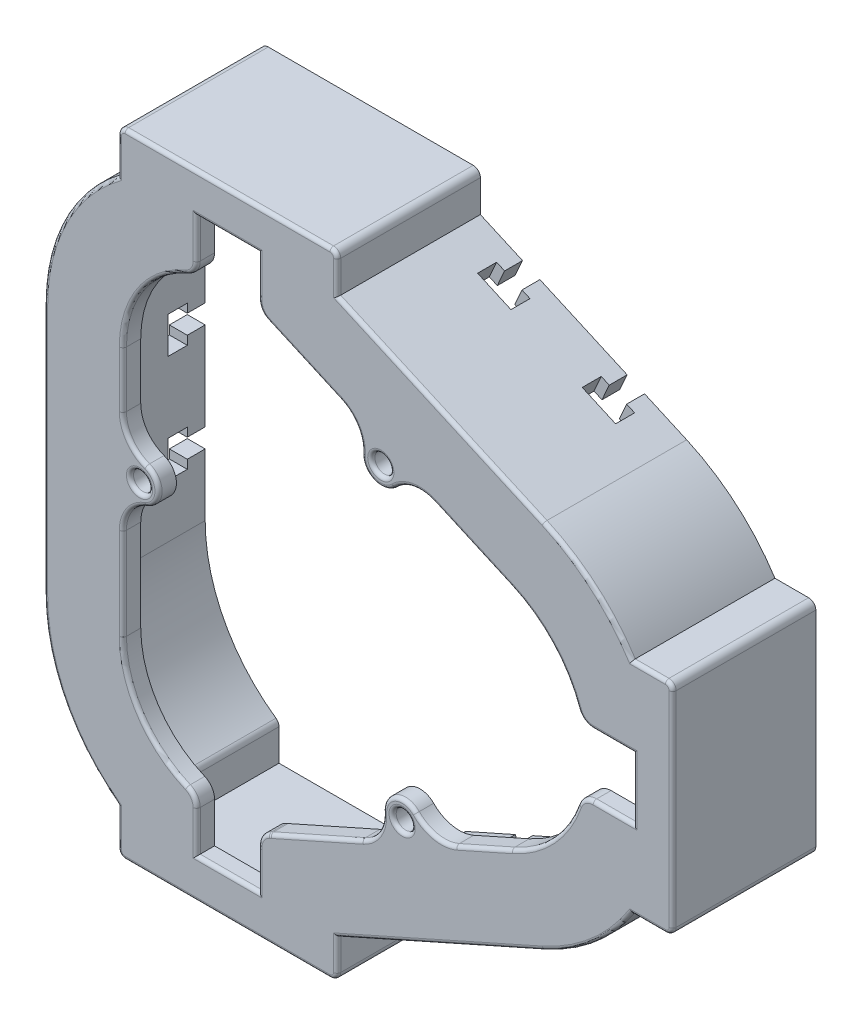
SolidWorks part; units mm, degrees
ref_plane "Front Plane" through (0, 0, 0) normal (0, 0, 1) x (1, 0, 0)
ref_plane "Top Plane" through (0, 0, 0) normal (0, 1, 0) x (1, 0, 0)
ref_plane "Right Plane" through (0, 0, 0) normal (1, 0, 0) x (0, 0, -1)
sketch "Sketch1" plane through (0, 0, -80.01) normal (0, 0, -1) x (-1, 0, 0)
  line L0 (14.1705, 137.7093) -> (22.108, 137.7093) construction
  line L1 (-128.3273, 40.8549) -> (-128.3273, 32.9174) construction
  line L2 (14.1705, -63.937) -> (22.108, -63.937) construction
  line L3 (55.2868, -7.5638) -> (55.2868, 81.3362)
  line L4 (29.093, 120.8247) -> (29.093, 135.1693)
  line L5 (29.093, 135.1693) -> (22.108, 135.1693)
  line L6 (14.1705, 135.1693) -> (22.108, 135.1693)
  line L7 (14.1705, 135.1693) -> (7.1855, 135.1693)
  line L8 (7.1855, 135.1693) -> (7.1855, 120.8247)
  line L9 (3.0278, 115.2711) -> (-82.5915, 77.144)
  line L10 (-111.5749, 47.8399) -> (-125.7873, 47.8399)
  line L11 (-125.7873, 47.8399) -> (-125.7873, 40.8549)
  line L12 (-125.7873, 40.8549) -> (-125.7873, 32.9174)
  line L13 (-125.7873, 32.9174) -> (-125.7873, 25.9324)
  line L14 (-125.7873, 25.9324) -> (-111.5749, 25.9324)
  line L15 (-82.5915, -3.3716) -> (3.0278, -41.4987)
  line L16 (7.1855, -47.0524) -> (7.1855, -61.397)
  line L17 (7.1855, -61.397) -> (14.1705, -61.397)
  line L18 (14.1705, -61.397) -> (22.108, -61.397)
  line L19 (22.108, -61.397) -> (29.093, -61.397)
  line L20 (29.093, -61.397) -> (29.093, -47.0524)
  line L21 (57.8268, -7.5638) -> (57.8268, 81.3362)
  line L22 (31.633, 120.8247) -> (31.633, 137.7093)
  line L23 (31.633, 137.7093) -> (22.108, 137.7093)
  line L24 (22.108, 137.7093) -> (22.108, 117.6323)
  line L25 (14.1705, 117.6323) -> (14.1705, 137.7093)
  line L26 (14.1705, 137.7093) -> (4.6455, 137.7093)
  line L27 (4.6455, 137.7093) -> (4.6455, 120.8247)
  line L28 (1.9945, 117.5914) -> (-83.6248, 79.4643)
  line L29 (-111.5749, 50.3799) -> (-128.3273, 50.3799)
  line L30 (-128.3273, 50.3799) -> (-128.3273, 40.8549)
  line L31 (-128.3273, 40.8549) -> (-106.0032, 40.8549)
  line L32 (-106.0032, 32.9174) -> (-128.3273, 32.9174)
  line L33 (-128.3273, 32.9174) -> (-128.3273, 23.3924)
  line L34 (-128.3273, 23.3924) -> (-111.5749, 23.3924)
  line L35 (-83.6248, -5.692) -> (1.9945, -43.8191)
  line L36 (4.6455, -47.0524) -> (4.6455, -63.937)
  line L37 (4.6455, -63.937) -> (14.1705, -63.937)
  line L38 (14.1705, -63.937) -> (14.1705, -43.86)
  line L39 (22.108, -43.86) -> (22.108, -63.937)
  line L40 (22.108, -63.937) -> (31.633, -63.937)
  line L41 (31.633, -63.937) -> (31.633, -47.0524)
  line L42 (57.8268, -7.5638) -> (57.8268, 81.3362) construction
  line L43 (31.633, 120.8247) -> (31.633, 137.7093) construction
  line L44 (31.633, 137.7093) -> (22.108, 137.7093) construction
  line L47 (14.1705, 137.7093) -> (4.6455, 137.7093) construction
  line L48 (4.6455, 137.7093) -> (4.6455, 120.8247) construction
  line L49 (1.9945, 117.5914) -> (-83.6248, 79.4643) construction
  line L50 (-111.5749, 50.3799) -> (-128.3273, 50.3799) construction
  line L51 (-128.3273, 50.3799) -> (-128.3273, 40.8549) construction
  line L54 (-128.3273, 32.9174) -> (-128.3273, 23.3924) construction
  line L55 (-128.3273, 23.3924) -> (-111.5749, 23.3924) construction
  line L56 (-83.6248, -5.692) -> (1.9945, -43.8191) construction
  line L57 (4.6455, -47.0524) -> (4.6455, -63.937) construction
  line L58 (4.6455, -63.937) -> (14.1705, -63.937) construction
  line L61 (22.108, -63.937) -> (31.633, -63.937) construction
  line L62 (31.633, -63.937) -> (31.633, -47.0524) construction
  line L63 (83.2268, -7.5638) -> (83.2268, 81.3362)
  line L64 (57.033, 133.5249) -> (57.033, 149.1393)
  line L65 (57.033, 149.1393) -> (22.108, 149.1393)
  line L66 (14.1705, 149.1393) -> (22.108, 149.1393)
  line L67 (14.1705, 149.1393) -> (-20.7545, 149.1393)
  line L68 (-20.7545, 149.1393) -> (-20.7545, 135.2657)
  line L69 (-20.7545, 135.2657) -> (-93.9575, 102.6677)
  line L70 (-125.2661, 75.7799) -> (-139.7573, 75.7799)
  line L71 (-139.7573, 75.7799) -> (-139.7573, 40.8549)
  line L72 (-139.7573, 40.8549) -> (-139.7573, 32.9174)
  line L73 (-139.7573, 32.9174) -> (-139.7573, -2.0076)
  line L74 (-139.7573, -2.0076) -> (-125.2661, -2.0076)
  line L75 (-93.9575, -28.8953) -> (-20.7545, -61.4933)
  line L76 (-20.7545, -61.4933) -> (-20.7545, -75.367)
  line L77 (-20.7545, -75.367) -> (14.1705, -75.367)
  line L78 (14.1705, -75.367) -> (22.108, -75.367)
  line L79 (22.108, -75.367) -> (57.033, -75.367)
  line L80 (57.033, -75.367) -> (57.033, -59.7525)
  line L81 (76.8768, -7.5638) -> (76.8768, 81.3362)
  line L82 (50.683, 130.234) -> (50.683, 142.7893)
  line L83 (50.683, 142.7893) -> (22.108, 142.7893)
  line L84 (14.1705, 142.7893) -> (22.108, 142.7893)
  line L85 (14.1705, 142.7893) -> (-14.4045, 142.7893)
  line L86 (-14.4045, 142.7893) -> (-14.4045, 131.1423)
  line L87 (-14.4045, 131.1423) -> (-91.3743, 96.8669)
  line L88 (-121.6907, 69.4299) -> (-133.4073, 69.4299)
  line L89 (-133.4073, 69.4299) -> (-133.4073, 40.8549)
  line L90 (-133.4073, 40.8549) -> (-133.4073, 32.9174)
  line L91 (-133.4073, 32.9174) -> (-133.4073, 4.3424)
  line L92 (-133.4073, 4.3424) -> (-121.6907, 4.3424)
  line L93 (-91.3743, -23.0945) -> (-14.4045, -57.3699)
  line L94 (-14.4045, -57.3699) -> (-14.4045, -69.017)
  line L95 (-14.4045, -69.017) -> (14.1705, -69.017)
  line L96 (14.1705, -69.017) -> (29.5517, -69.017)
  line L97 (29.5517, -69.017) -> (50.683, -69.017)
  line L98 (50.683, -69.017) -> (50.683, -56.4617)
  line L99 (49.3813, 43.2476) -> (49.3813, 81.3362) construction
  line L100 (49.3813, 81.3362) -> (57.8268, 81.3362) construction
  line L101 (14.1705, -69.017) -> (14.1705, -63.937) construction
  line L102 (-133.4073, 40.8549) -> (-128.3273, 40.8549) construction
  line L103 (14.1705, -69.017) -> (14.1705, -75.367) construction
  line L104 (-133.4073, 40.8549) -> (-139.7573, 40.8549) construction
  line L105 (22.108, 137.7093) -> (22.108, 142.7893) construction
  line L106 (22.108, 149.1393) -> (22.108, 142.7893) construction
  circle A3 centre (18.1393, 81.3362) radius 19.05 construction
  circle A4 centre (18.1393, -7.5638) radius 47.625 construction
  circle A5 centre (-58.3701, 37.7264) radius 19.05 construction
  arc A6 (-29.3254, 43.8149) -> (-88.2162, 25.2292) centre (-58.7708, 34.522) ccw construction
  arc A7 (-29.3254, 43.8149) -> (-88.2162, 25.2292) centre (-58.7708, 34.522) ccw construction
  arc A8 (-89.1699, 24.9282) -> (-28.3718, 44.1159) centre (-58.7708, 34.522) ccw construction
  arc A9 (-89.1699, 24.9282) -> (-28.3718, 44.1159) centre (-58.7708, 34.522) ccw construction
  circle A10 centre (18.1393, 76.2562) radius 36.5125 construction
  circle A11 centre (18.1393, 76.2562) radius 36.5125 construction
  circle A12 centre (49.3813, 43.2476) radius 3.3782
  circle A13 centre (-43.805, -14.1791) radius 3.3782
  circle A14 centre (-36.2365, 91.4312) radius 3.3782
  arc A15 (33.5733, -44.1273) -> (57.8268, -7.5638) centre (18.1393, -7.5638) ccw
  arc A16 (57.8268, 81.3362) -> (33.5733, 117.8997) centre (18.1393, 81.3362) ccw
  arc A17 (31.633, 120.8247) -> (33.5733, 117.8997) centre (34.808, 120.8247) ccw
  arc A18 (14.1705, 117.6323) -> (22.108, 117.6323) centre (18.1393, 81.3362) ccw
  arc A19 (2.7053, 117.8997) -> (4.6455, 120.8247) centre (1.4705, 120.8247) ccw
  arc A20 (2.7053, 117.8997) -> (1.9945, 117.5914) centre (18.1393, 81.3362) ccw
  arc A21 (-83.6248, 79.4643) -> (-108.5831, 52.4919) centre (-64.6643, 36.8862) ccw
  arc A22 (-111.5749, 50.3799) -> (-108.5831, 52.4919) centre (-111.5749, 53.5549) ccw
  arc A23 (-106.0032, 32.9174) -> (-106.0032, 40.8549) centre (-64.6643, 36.8862) ccw
  arc A24 (-108.5831, 21.2805) -> (-111.5749, 23.3924) centre (-111.5749, 20.2174) ccw
  arc A25 (-108.5831, 21.2805) -> (-83.6248, -5.692) centre (-64.6643, 36.8862) ccw
  arc A26 (1.9945, -43.8191) -> (2.7053, -44.1273) centre (18.1393, -7.5638) ccw
  arc A27 (4.6455, -47.0524) -> (2.7053, -44.1273) centre (1.4705, -47.0524) ccw
  arc A28 (22.108, -43.86) -> (14.1705, -43.86) centre (18.1393, -7.5638) ccw
  arc A29 (33.5733, -44.1273) -> (31.633, -47.0524) centre (34.808, -47.0524) ccw
  arc A30 (33.5733, -44.1273) -> (57.8268, -7.5638) centre (18.1393, -7.5638) ccw construction
  arc A31 (57.8268, 81.3362) -> (33.5733, 117.8997) centre (18.1393, 81.3362) ccw construction
  arc A32 (31.633, 120.8247) -> (33.5733, 117.8997) centre (34.808, 120.8247) ccw construction
  arc A34 (2.7053, 117.8997) -> (4.6455, 120.8247) centre (1.4705, 120.8247) ccw construction
  arc A35 (2.7053, 117.8997) -> (1.9945, 117.5914) centre (18.1393, 81.3362) ccw construction
  arc A36 (-83.6248, 79.4643) -> (-108.5831, 52.4919) centre (-64.6643, 36.8862) ccw construction
  arc A37 (-111.5749, 50.3799) -> (-108.5831, 52.4919) centre (-111.5749, 53.5549) ccw construction
  arc A39 (-108.5831, 21.2805) -> (-111.5749, 23.3924) centre (-111.5749, 20.2174) ccw construction
  arc A40 (-108.5831, 21.2805) -> (-83.6248, -5.692) centre (-64.6643, 36.8862) ccw construction
  arc A41 (1.9945, -43.8191) -> (2.7053, -44.1273) centre (18.1393, -7.5638) ccw construction
  arc A42 (4.6455, -47.0524) -> (2.7053, -44.1273) centre (1.4705, -47.0524) ccw construction
  arc A44 (33.5733, -44.1273) -> (31.633, -47.0524) centre (34.808, -47.0524) ccw construction
  arc A45 (-25.2473, 23.811) -> (-27.1386, 19.0962) centre (-64.6643, 36.8862) ccw construction
  arc A46 (-25.2473, 23.811) -> (-27.1386, 19.0962) centre (-64.6643, 36.8862) ccw construction
  circle A47 centre (-43.805, -14.1791) radius 6.7564
  circle A48 centre (49.3813, 43.2476) radius 6.7564
  circle A49 centre (-36.2365, 91.4312) radius 6.7564
  arc A50 (32.5855, -41.7872) -> (55.2868, -7.5638) centre (18.1393, -7.5638) ccw
  arc A51 (55.2868, 81.3362) -> (32.5855, 115.5596) centre (18.1393, 81.3362) ccw
  arc A52 (29.093, 120.8247) -> (32.5855, 115.5596) centre (34.808, 120.8247) ccw
  arc A53 (3.693, 115.5596) -> (7.1855, 120.8247) centre (1.4705, 120.8247) ccw
  arc A54 (3.693, 115.5596) -> (3.0278, 115.2711) centre (18.1393, 81.3362) ccw
  arc A55 (-82.5915, 77.144) -> (-106.1897, 51.6414) centre (-64.6643, 36.8862) ccw
  arc A56 (-111.5749, 47.8399) -> (-106.1897, 51.6414) centre (-111.5749, 53.5549) ccw
  arc A57 (-106.1897, 22.1309) -> (-111.5749, 25.9324) centre (-111.5749, 20.2174) ccw
  arc A58 (-106.1897, 22.1309) -> (-82.5915, -3.3716) centre (-64.6643, 36.8862) ccw
  arc A59 (3.0278, -41.4987) -> (3.693, -41.7872) centre (18.1393, -7.5638) ccw
  arc A60 (7.1855, -47.0524) -> (3.693, -41.7872) centre (1.4705, -47.0524) ccw
  arc A61 (32.5855, -41.7872) -> (29.093, -47.0524) centre (34.808, -47.0524) ccw
  arc A62 (57.033, -59.7525) -> (83.2268, -7.5638) centre (18.1393, -7.5638) ccw
  arc A63 (83.2268, 81.3362) -> (57.033, 133.5249) centre (18.1393, 81.3362) ccw
  arc A67 (-93.9575, 102.6677) -> (-125.2661, 75.7799) centre (-64.6643, 36.8862) ccw
  arc A70 (-125.2661, -2.0076) -> (-93.9575, -28.8953) centre (-64.6643, 36.8862) ccw
  arc A74 (50.683, -56.4617) -> (76.8768, -7.5638) centre (18.1393, -7.5638) ccw
  arc A75 (76.8768, 81.3362) -> (50.683, 130.234) centre (18.1393, 81.3362) ccw
  arc A79 (-91.3743, 96.8669) -> (-121.6907, 69.4299) centre (-64.6643, 36.8862) ccw
  arc A82 (-121.6907, 4.3424) -> (-91.3743, -23.0945) centre (-64.6643, 36.8862) ccw
  point P29 (21.8611, -69.017)
  point P68 (-40.8151, 98.5279)
  arc M83 (33.5733, -44.1273) -> (57.8268, -7.5638) centre (18.1393, -7.5638) ccw
  line M84 (57.8268, -7.5638) -> (57.8268, 81.3362)
  arc M85 (57.8268, 81.3362) -> (33.5733, 117.8997) centre (18.1393, 81.3362) ccw
  arc M86 (33.5733, 117.8997) -> (31.633, 120.8247) centre (34.808, 120.8247) cw
  line M87 (31.633, 120.8247) -> (31.633, 137.7093)
  line M88 (31.633, 137.7093) -> (22.108, 137.7093)
  line M89 (22.108, 137.7093) -> (22.108, 117.6323)
  line M91 (14.1705, 117.6323) -> (14.1705, 137.7093)
  line M92 (14.1705, 137.7093) -> (4.6455, 137.7093)
  line M93 (4.6455, 137.7093) -> (4.6455, 120.8247)
  arc M94 (4.6455, 120.8247) -> (2.7053, 117.8997) centre (1.4705, 120.8247) cw
  arc M95 (2.7053, 117.8997) -> (1.9945, 117.5914) centre (18.1393, 81.3362) ccw
  line M96 (1.9945, 117.5914) -> (-83.6248, 79.4643)
  arc M97 (-83.6248, 79.4643) -> (-108.5831, 52.4919) centre (-64.6643, 36.8862) ccw
  arc M98 (-108.5831, 52.4919) -> (-111.5749, 50.3799) centre (-111.5749, 53.5549) cw
  line M99 (-111.5749, 50.3799) -> (-128.3273, 50.3799)
  line M100 (-128.3273, 50.3799) -> (-128.3273, 40.8549)
  line M101 (-128.3273, 40.8549) -> (-106.0032, 40.8549)
  line M103 (-106.0032, 32.9174) -> (-128.3273, 32.9174)
  line M104 (-128.3273, 32.9174) -> (-128.3273, 23.3924)
  line M105 (-128.3273, 23.3924) -> (-111.5749, 23.3924)
  arc M106 (-111.5749, 23.3924) -> (-108.5831, 21.2805) centre (-111.5749, 20.2174) cw
  arc M107 (-108.5831, 21.2805) -> (-83.6248, -5.692) centre (-64.6643, 36.8862) ccw
  line M108 (-83.6248, -5.692) -> (1.9945, -43.8191)
  arc M109 (1.9945, -43.8191) -> (2.7053, -44.1273) centre (18.1393, -7.5638) ccw
  arc M110 (2.7053, -44.1273) -> (4.6455, -47.0524) centre (1.4705, -47.0524) cw
  line M111 (4.6455, -47.0524) -> (4.6455, -63.937)
  line M112 (4.6455, -63.937) -> (14.1705, -63.937)
  line M113 (14.1705, -63.937) -> (14.1705, -43.86)
  line M115 (22.108, -43.86) -> (22.108, -63.937)
  line M116 (22.108, -63.937) -> (31.633, -63.937)
  line M117 (31.633, -63.937) -> (31.633, -47.0524)
  arc M118 (31.633, -47.0524) -> (33.5733, -44.1273) centre (34.808, -47.0524) cw
  dimension "D2" = 6.7564
  dimension "D3" = 8.4455
  dimension "D4" = 8.4455
  dimension "D6" = 3.3782
  dimension "D5" = 38.0886
  dimension "D10" = 8.4455
  dimension "D8" = 5.08
  dimension "D9" = 6.35
  dimension "D1" = 0
  dimension "D7" = 2.54
extrude "Boss-Extrude1" add sketch "Sketch1" along normal blind 6.35 contours L3 A48 A12 | L9 A49 A14 | L15 A47 A13 | L92 A82 L93 L94 L95 L96 L97 L98 A74 L81 A75 L82 L83 L84 L85 L86 L87 A79 L88 L89 L90 L91 L18 L12 L6 M113 M112 M111 M110 M109 M108 M107 M106 M105 M104 M103 M101 M100 M99 M98 M97 M96 M95 M94 M93 M92 M91 M89 M88 M87 | L16 A60 A59 L15 A47 A58 A57 L14 L13 L17 M103 M104 M105 M106 M107 M108 M109 M110 M111 M112 M113 | A50 A61 L20 L19 L5 L4 A52 A51 L3 A48 M115 M116 M117 M118 M83 M84 M85 M86 M87 M88 M89 | L10 A56 A55 L9 A49 A54 A53 L8 L7 L11 M91 M92 M93 M94 M95 M96 M97 M98 M99 M100 M101 | L74 A70 L75 L76 L77 L78 L79 L80 A62 L63 A63 L64 L65 L66 L67 L68 L69 A67 L70 L71 L72 L73 A82 L92 L91 L90 L89 L88 A79 L87 L86 L85 L84 L83 L82 A75 L81 A74 L98 L97 L96 L95 L94 L93 | L3 A48 | L9 A49 | L15 A47 region at (-57.3347, 16.2007, -80.01) region at (-42.8101, 43.2476, -80.01) region at (-55.6291, 43.2476, -80.01) region at (-12.4476, -62.667, -80.01) region at (-10.678, 136.8923, -80.01) region at (46.3466, -19.8865, -80.01) region at (46.1297, -19.3994, -80.01) region at (31.3282, 95.7919, -80.01) region at (38.7539, 97.0843, -80.01) region at (-73.4829, -35.341, -80.01) region at (-67.285, -33.8903, -80.01)
extrude "Boss-Extrude2" add sketch "Sketch1<3>" along normal blind 50.8 contours L74 A70 L75 L76 L77 L78 L79 L80 A62 L63 A63 L64 L65 L66 L67 L68 L69 A67 L70 L71 L72 L73 A82 L92 L91 L90 L89 L88 A79 L87 L86 L85 L84 L83 L82 A75 L81 A74 L98 L97 L96 L95 L94 L93 region at (-73.4829, -35.341, -80.01)
sketch "Sketch1<3>" plane through (0, 0, -80.01) normal (0, 0, -1) x (-1, 0, 0) same geometry as "Sketch1"
sketch "Sketch2" plane through (-83.2268, 0, 0) normal (-1, 0, 0) x (0, 0, 1)
  line L0 (-80.01, 36.8862) -> (-130.81, 36.8862) construction
  line L1 (-130.81, 395.458) -> (-130.81, 402.2144)
  line L2 (-80.01, -7.5638) -> (-80.01, 81.3362) construction
  line L3 (-130.81, -7.5638) -> (-130.81, 81.3362) construction
  line L4 (-130.81, 52.558) -> (-124.46, 52.558)
  line L5 (-124.46, 52.558) -> (-124.46, 49.4592)
  line L6 (-124.46, 49.4592) -> (-117.602, 49.4592)
  line L7 (-117.602, 49.4592) -> (-117.602, 62.4132)
  line L8 (-117.602, 55.9362) -> (-130.81, 55.9362) construction
  line L9 (-124.46, 62.4132) -> (-117.602, 62.4132)
  line L10 (-130.81, 59.3144) -> (-124.46, 59.3144)
  line L11 (-124.46, 59.3144) -> (-124.46, 62.4132)
  line L12 (-130.81, 14.458) -> (-124.46, 14.458)
  line L13 (-124.46, 14.458) -> (-124.46, 11.3592)
  line L14 (-124.46, 11.3592) -> (-117.602, 11.3592)
  line L15 (-117.602, 24.3132) -> (-117.602, 11.3592)
  line L16 (-124.46, 24.3132) -> (-117.602, 24.3132)
  line L17 (-124.46, 21.2144) -> (-124.46, 24.3132)
  line L18 (-130.81, 21.2144) -> (-124.46, 21.2144)
  line L19 (-130.81, 14.458) -> (-130.81, 21.2144)
  line L20 (-130.81, 52.558) -> (-130.81, 59.3144)
  line L21 (-130.81, 402.2144) -> (-124.46, 402.2144)
  line L22 (-124.46, 402.2144) -> (-124.46, 405.3132)
  line L23 (-124.46, 405.3132) -> (-117.602, 405.3132)
  line L24 (-117.602, 405.3132) -> (-117.602, 392.3592)
  line L25 (-124.46, 392.3592) -> (-117.602, 392.3592)
  line L26 (-124.46, 395.458) -> (-124.46, 392.3592)
  line L27 (-130.81, 395.458) -> (-124.46, 395.458)
  line L28 (-130.81, 433.558) -> (-130.81, 440.3144)
  line L29 (-130.81, 440.3144) -> (-124.46, 440.3144)
  line L30 (-124.46, 440.3144) -> (-124.46, 443.4132)
  line L31 (-124.46, 443.4132) -> (-117.602, 443.4132)
  line L32 (-117.602, 430.4592) -> (-117.602, 443.4132)
  line L33 (-124.46, 430.4592) -> (-117.602, 430.4592)
  line L34 (-124.46, 433.558) -> (-124.46, 430.4592)
  line L35 (-130.81, 433.558) -> (-124.46, 433.558)
  dimension "D1" = 6.858
  dimension "D2" = 6.7564
  dimension "D3" = 6.35
  dimension "D4" = 19.05
  dimension "D6" = 6.477
  dimension "D5" = 2
sketch "Sketch3" plane through (53.7017, 120.594, 0) normal (0.4068, 0.9135, 0) x (0.9135, -0.4068, 0)
  line L0 (4.0002, 130.81) -> (4.0002, 80.01) construction
  line L1 (-36.0663, 130.81) -> (44.0668, 130.81) construction
  line L2 (-36.0663, 80.01) -> (44.0668, 80.01) construction
  line L3 (24.3202, 130.81) -> (24.3202, 117.7036) construction
  line L4 (20.942, 130.81) -> (20.942, 124.46)
  line L5 (20.942, 124.46) -> (17.8432, 124.46)
  line L6 (17.8432, 124.46) -> (17.8432, 117.7036)
  line L7 (17.8432, 117.7036) -> (30.7972, 117.7036)
  line L8 (30.7972, 124.46) -> (30.7972, 117.7036)
  line L9 (27.6984, 124.46) -> (30.7972, 124.46)
  line L10 (27.6984, 130.81) -> (27.6984, 124.46)
  line L11 (-16.3198, 130.81) -> (-16.3198, 117.7036) construction
  line L12 (-19.698, 130.81) -> (-19.698, 124.46)
  line L13 (-12.9416, 130.81) -> (-12.9416, 124.46)
  line L14 (-19.698, 124.46) -> (-22.7968, 124.46)
  line L15 (-22.7968, 124.46) -> (-22.7968, 117.7036)
  line L16 (-12.9416, 124.46) -> (-9.8428, 124.46)
  line L17 (-9.8428, 124.46) -> (-9.8428, 117.7036)
  line L18 (-9.8428, 117.7036) -> (-22.7968, 117.7036)
  line L19 (-19.698, 130.81) -> (-12.9416, 130.81)
  line L20 (20.942, 130.81) -> (27.6984, 130.81)
  dimension "D1" = 3.3782
  dimension "D2" = 6.7564
  dimension "D3" = 6.35
  dimension "D4" = 6.477
  dimension "D5" = 20.32
extrude "Cut-Extrude1" cut sketch "Sketch3" against normal blind 18.542
ref_plane "Plane4" through (0, 36.8862, 0) normal (0, 1, 0) x (1, 0, 0)
mirror "Mirror1" about plane through (0, 36.8862, 0) normal (0, 1, 0) of "Cut-Extrude1"
extrude "Cut-Extrude2" cut sketch "Sketch2" against normal blind 18.542
fillet "Fillet1" radius 12.7 6 edges at (49.2059, -18.2386, -83.185) (43.2089, -20.9091, -83.185) (-55.2868, 46.53, -83.185) (-55.2868, 39.9652, -83.185) (41.7555, 95.3287, -83.185) (35.4409, 98.1406, -83.185)
fillet "Fillet2" radius 2.54 16 edges at (133.4073, 69.4299, -108.585) (133.4073, 4.3424, -108.585) (14.4045, 142.7893, -108.585) (-50.683, 142.7893, -108.585) (14.4045, 131.1423, -108.585) (-50.683, 130.234, -108.585) (14.4045, -57.3699, -108.585) (-50.683, -56.4617, -108.585) (20.7545, -75.367, -105.41) (-57.033, -75.367, -105.41) (-57.033, 149.1393, -105.41) (20.7545, 149.1393, -105.41) (139.7573, 75.7799, -105.41) (139.7573, -2.0076, -105.41) (121.6907, 4.3424, -108.585) (121.6907, 69.4299, -108.585)
fillet "Fillet3" radius 1.27 61 edges at (-56.2891, -74.623, -80.01) (-57.033, -66.2897, -80.01) (-76.3109, -36.7604, -80.01) (-83.2268, 36.8862, -80.01) (-76.3109, 110.5328, -80.01) (-57.033, 140.0621, -80.01) (-56.2891, 148.3954, -80.01) (-18.1393, 149.1393, -80.01) (20.0105, 148.3954, -80.01) (20.7545, 140.9325, -80.01) (57.356, 118.9667, -80.01) (111.5792, 91.5148, -80.01) (131.2417, 75.7799, -80.01) (139.0133, 75.036, -80.01) (139.7573, 36.8862, -80.01) (139.0133, -1.2636, -80.01) (131.2417, -2.0076, -80.01) (111.5792, -17.7424, -80.01) (57.356, -45.1943, -80.01) (20.7545, -67.1601, -80.01) (20.0105, -74.623, -80.01) (-18.1393, -75.367, -80.01) (32.8583, 91.4312, -80.01) (-52.7595, 43.2476, -80.01) (40.4268, -14.1791, -80.01) (118.6811, 47.8399, -80.01) (108.279, 48.886, -80.01) (97.0101, 66.8166, -80.01) (68.9051, 83.2387, -80.01) (47.712, 90.2142, -80.01) (33.488, 85.2591, -80.01) (27.6546, 99.1459, -80.01) (9.475, 109.7035, -80.01) (-3.3597, 115.417, -80.01) (-6.233, 117.6657, -80.01) (-7.1855, 127.997, -80.01) (-18.1393, 135.1693, -80.01) (-29.093, 127.997, -80.01) (-30.0455, 117.6657, -80.01) (-49.0955, 101.8702, -80.01) (-55.2868, 71.4076, -80.01) (-53.0179, 54.2346, -80.01) (-42.6249, 43.2476, -80.01) (-53.0179, 32.2606, -80.01) (-55.2868, 8.7262, -80.01) (-49.0955, -28.0979, -80.01) (-30.0455, -43.8933, -80.01) (-29.093, -54.2247, -80.01) (-18.1393, -61.397, -80.01) (-7.1855, -54.2247, -80.01) (-6.233, -43.8933, -80.01) (-3.3597, -41.6446, -80.01) (13.2624, -34.2446, -80.01) (35.2476, -21.9706, -80.01) (41.0565, -8.007, -80.01) (55.3212, -13.0317, -80.01) (72.7268, -7.7645, -80.01) (97.0101, 6.9558, -80.01) (108.279, 24.8863, -80.01) (118.6811, 25.9324, -80.01) (125.7873, 36.8862, -80.01)
equation "\"D4@Sketch1\"=\"D3@Sketch1\""
equation "\"D10@Sketch1\"=\"D3@Sketch1\""
